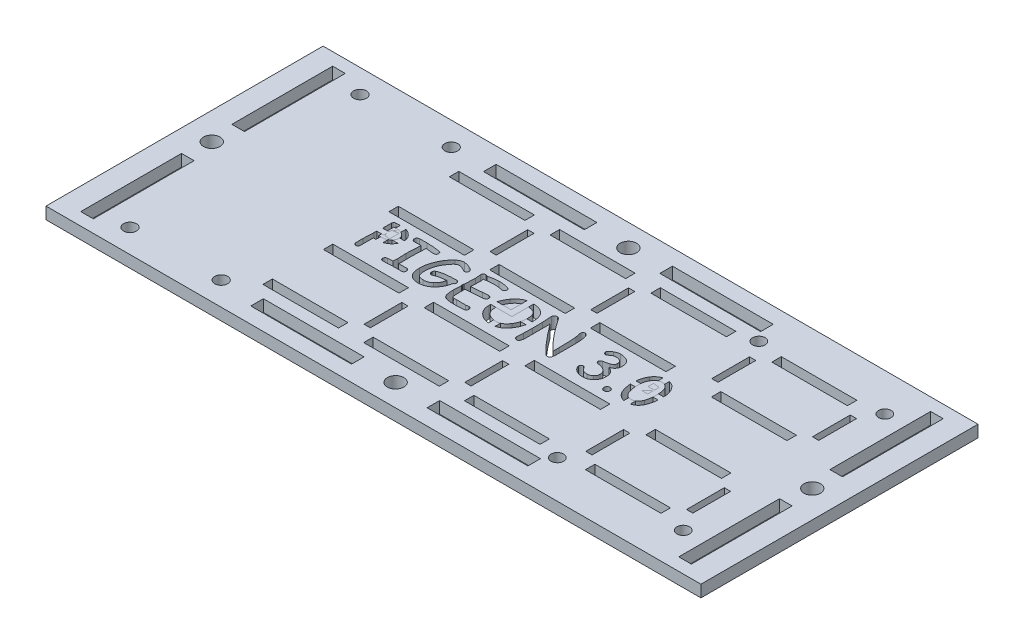
SolidWorks part; units mm, degrees
material "Thornel VCB-20 Carbon Cloth"
ref_plane "Front Plane" through (0, 0, 0) normal (0, 0, 1) x (1, 0, 0)
ref_plane "Top Plane" through (0, 0, 0) normal (0, 1, 0) x (1, 0, 0)
ref_plane "Right Plane" through (0, 0, 0) normal (1, 0, 0) x (0, 0, -1)
sketch "Sketch1" plane through (0, 0, 0) normal (0, 1, 0) x (1, 0, 0)
  line L1 (-82.55, -34.925) -> (82.55, -34.925)
  line L2 (-82.55, -34.925) -> (-82.55, 34.925)
  line L3 (-82.55, 34.925) -> (82.55, 34.925)
  line L4 (82.55, -34.925) -> (82.55, 34.925)
  dimension "D1" = 69.85
  dimension "D2" = 165.1
  dimension "D3" = 34.925
  dimension "D4" = 82.55
extrude "Boss-Extrude1" add sketch "Sketch1" along normal blind 3
sketch "Sketch2" plane through (0, 3, 0) normal (0, 1, 0) x (1, 0, 0)
  line L0 (-82.55, 34.925) -> (-82.55, -34.925) construction
  line L1 (82.55, -34.925) -> (82.55, 34.925) construction
  line L2 (82.55, 34.925) -> (-82.55, 34.925) construction
  line L3 (-82.55, -34.925) -> (82.55, -34.925) construction
  circle A0 centre (-77.47, 29.845) radius 1.5
  circle A1 centre (-77.47, -29.845) radius 1.5
  circle A2 centre (77.47, 29.845) radius 1.5
  circle A3 centre (77.47, -29.845) radius 1.5
  dimension "D1" = 3
  dimension "D2" = 3
  dimension "D3" = 3
  dimension "D4" = 3
  dimension "D5" = 5.08
  dimension "D6" = 5.08
  dimension "D7" = 5.08
  dimension "D8" = 5.08
  dimension "D9" = 5.08
  dimension "D10" = 5.08
  dimension "D11" = 5.08
  dimension "D12" = 5.08
sketch "Sketch3" plane through (0, 3, 0) normal (0, 1, 0) x (1, 0, 0)
  line L0 (-82.55, 34.925) -> (-82.55, -34.925) construction
  line L1 (82.55, -34.925) -> (82.55, 34.925) construction
  line L2 (-82.55, -34.925) -> (82.55, -34.925) construction
  line L3 (82.55, 34.925) -> (-82.55, 34.925) construction
  circle A0 centre (-75.692, 0) radius 2.0828
  circle A1 centre (75.692, 0) radius 2.0828
  circle A2 centre (0, -29.337) radius 2.0828
  circle A3 centre (0, 29.337) radius 2.0828
  dimension "D1" = 6.858
  dimension "D2" = 6.858
  dimension "D3" = 5.588
  dimension "D4" = 5.588
extrude "Cut-Extrude2" cut sketch "Sketch3" against normal blind 5.08
sketch "Sketch4" plane through (0, 3, 0) normal (0, 1, 0) x (1, 0, 0)
  line L0 (-82.55, 34.925) -> (-82.55, -34.925) construction
  line L1 (-44.31, -29) -> (-67.31, -29) construction
  line L2 (-44.31, -29) -> (-44.31, 29) construction
  line L3 (-44.31, 29) -> (-67.31, 29) construction
  line L4 (-67.31, -29) -> (-67.31, 29) construction
  line L5 (-44.31, -29) -> (-67.31, 29) construction
  line L6 (-44.31, 29) -> (-67.31, -29) construction
  circle A0 centre (-67.31, 29) radius 1.625
  circle A1 centre (-44.31, 29) radius 1.625
  circle A2 centre (-44.31, -29) radius 1.625
  circle A3 centre (-67.31, -29) radius 1.625
  point P0 (-55.81, 0)
  dimension "D3" = 3.25
  dimension "D1" = 58
  dimension "D2" = 23
  dimension "D4" = 15.24
extrude "Cut-Extrude3" cut sketch "Sketch4" against normal blind 17.78
sketch "Sketch5" plane through (0, 3, 0) normal (0, 1, 0) x (1, 0, 0)
  line L0 (82.55, 34.925) -> (-82.55, 34.925) construction
  line L1 (68.58, -25.4) -> (36.83, -25.4) construction
  line L2 (68.58, -25.4) -> (68.58, 25.4) construction
  line L3 (68.58, 25.4) -> (36.83, 25.4) construction
  line L4 (36.83, -25.4) -> (36.83, 25.4) construction
  line L5 (68.58, -25.4) -> (36.83, 25.4) construction
  line L6 (68.58, 25.4) -> (36.83, -25.4) construction
  line L7 (-82.55, -34.925) -> (82.55, -34.925) construction
  line L8 (82.55, -34.925) -> (82.55, 34.925) construction
  circle A0 centre (68.58, -25.4) radius 1.5875
  circle A2 centre (68.58, 25.4) radius 1.5875
  circle A3 centre (36.83, 25.4) radius 1.5875
  circle A4 centre (36.83, -25.4) radius 1.5875
  point P0 (52.705, 0)
  dimension "D1" = 9.525
  dimension "D3" = 3.175
  dimension "D2" = 9.525
  dimension "D4" = 31.75
  dimension "D5" = 13.97
extrude "Cut-Extrude4" cut sketch "Sketch5" against normal blind 7.874
sketch "Sketch6" plane through (0, 3, 0) normal (0, 1, 0) x (1, 0, 0)
  line L0 (82.55, 34.925) -> (-82.55, 34.925) construction
  line L1 (-34.925, 27.7495) -> (-9.525, 27.7495)
  line L2 (-34.925, 27.7495) -> (-34.925, 30.9245)
  line L3 (-34.925, 30.9245) -> (-9.525, 30.9245)
  line L4 (-9.525, 27.7495) -> (-9.525, 30.9245)
  line L5 (-34.925, 27.7495) -> (-9.525, 30.9245) construction
  line L6 (-34.925, 30.9245) -> (-9.525, 27.7495) construction
  line L7 (34.925, 30.9245) -> (34.925, 27.7495)
  line L8 (34.925, 30.9245) -> (9.525, 30.9245)
  line L9 (9.525, 30.9245) -> (9.525, 27.7495)
  line L10 (34.925, 27.7495) -> (9.525, 27.7495)
  line L11 (-34.925, -30.9245) -> (-34.925, -27.7495)
  line L12 (-34.925, -27.7495) -> (-9.525, -27.7495)
  line L13 (-9.525, -30.9245) -> (-9.525, -27.7495)
  line L14 (-34.925, -30.9245) -> (-9.525, -30.9245)
  line L15 (34.925, -27.7495) -> (34.925, -30.9245)
  line L16 (34.925, -27.7495) -> (9.525, -27.7495)
  line L17 (9.525, -27.7495) -> (9.525, -30.9245)
  line L18 (34.925, -30.9245) -> (9.525, -30.9245)
  line L19 (-82.55, 34.925) -> (-82.55, -34.925) construction
  line L20 (-76.962, 31.75) -> (-73.787, 31.75)
  line L21 (-76.962, 31.75) -> (-76.962, 6.35)
  line L22 (-76.962, 6.35) -> (-73.787, 6.35)
  line L23 (-73.787, 31.75) -> (-73.787, 6.35)
  line L24 (-76.962, 31.75) -> (-73.787, 6.35) construction
  line L25 (-76.962, 6.35) -> (-73.787, 31.75) construction
  line L26 (-76.962, -6.35) -> (-76.962, -31.75)
  line L27 (-76.962, -6.35) -> (-73.787, -6.35)
  line L28 (-73.787, -6.35) -> (-73.787, -31.75)
  line L29 (-76.962, -31.75) -> (-73.787, -31.75)
  line L30 (-82.55, -34.925) -> (82.55, -34.925) construction
  line L31 (76.962, -31.75) -> (76.962, -6.35)
  line L32 (76.962, -31.75) -> (73.787, -31.75)
  line L33 (73.787, -31.75) -> (73.787, -6.35)
  line L34 (76.962, -6.35) -> (73.787, -6.35)
  line L35 (76.962, 6.35) -> (76.962, 31.75)
  line L36 (76.962, 31.75) -> (73.787, 31.75)
  line L37 (73.787, 6.35) -> (73.787, 31.75)
  line L38 (76.962, 6.35) -> (73.787, 6.35)
  circle A0 centre (0, 29.337) radius 2.0828 construction
  point P0 (-22.225, 29.337)
  point P9 (-75.3745, 19.05)
  point P16 (0, 29.337)
  point P25 (0, 0)
  point P41 (0, 0)
  point P48 (0, 0)
  dimension "D1" = 5.588
  dimension "D2" = 3.175
  dimension "D3" = 25.4
  dimension "D4" = 22.225
  dimension "D7" = 5.588
  dimension "D8" = 3.175
  dimension "D9" = 25.4
  dimension "D10" = 3.175
  dimension "D12" = 3.175
  dimension "D11" = 2
  dimension "D5" = 2
  dimension "D6" = 2
  dimension "D13" = 2
extrude "Cut-Extrude5" cut sketch "Sketch6" against normal blind 10.922
sketch "Sketch7" plane through (0, 3, 0) normal (0, 1, 0) x (1, 0, 0)
  text T0 "PIGEON 3.0" font "Comic Sans MS" height 9.525
  point P1 (-47.03, 0)
  point P6 (-47.03, 0)
extrude "Cut-Extrude6" cut sketch "Sketch7" against normal blind 10.922
sketch "Sketch8" plane through (0, 3, 0) normal (0, 1, 0) x (1, 0, 0)
  line L0 (-37.8032, 1.2942) -> (-33.6782, 1.2942)
  line L1 (-37.8032, 1.2942) -> (-37.8032, 2.6847)
  line L2 (-37.8032, 2.6847) -> (-33.6782, 2.6847)
  line L3 (-27.9753, 1.2942) -> (-27.9753, 2.6847)
  line L4 (-33.6782, -3.5862) -> (-32.1004, -3.5862)
  line L5 (-33.6782, -3.5862) -> (-33.6782, 1.2942)
  line L6 (-33.6782, 7.5651) -> (-32.1004, 7.5651)
  line L7 (-32.1004, -3.5862) -> (-32.1004, 1.2942)
  line L8 (-32.1004, 2.6847) -> (-27.9753, 2.6847)
  line L9 (-33.6782, 2.6847) -> (-33.6782, 7.5651)
  line L10 (-32.1004, 1.2942) -> (-27.9753, 1.2942)
  line L11 (-32.1004, 2.6847) -> (-32.1004, 7.5651)
  line L12 (-5.3977, -0.3316) -> (-1.2727, -0.3316)
  line L13 (-5.3977, -0.3316) -> (-5.3977, 1.059)
  line L14 (-5.3977, 1.059) -> (-1.2727, 1.059)
  line L15 (4.4302, -0.3316) -> (4.4302, 1.059)
  line L16 (-1.2727, -5.212) -> (0.3051, -5.212)
  line L17 (-1.2727, -5.212) -> (-1.2727, -0.3316)
  line L18 (-1.2727, 5.9393) -> (0.3051, 5.9393)
  line L19 (0.3051, -5.212) -> (0.3051, -0.3316)
  line L20 (0.3051, 1.059) -> (4.4302, 1.059)
  line L21 (-1.2727, 1.059) -> (-1.2727, 5.9393)
  line L22 (0.3051, -0.3316) -> (4.4302, -0.3316)
  line L23 (0.3051, 1.059) -> (0.3051, 5.9393)
  line L24 (28.6195, -0.1096) -> (32.7445, -0.1096)
  line L25 (28.6195, -0.1096) -> (28.6195, 1.281)
  line L26 (28.6195, 1.281) -> (32.7445, 1.281)
  line L27 (38.4474, -0.1096) -> (38.4474, 1.281)
  line L28 (32.7445, -4.9899) -> (34.3223, -4.9899)
  line L29 (32.7445, -4.9899) -> (32.7445, -0.1096)
  line L30 (32.7445, 6.1614) -> (34.3223, 6.1614)
  line L31 (34.3223, -4.9899) -> (34.3223, -0.1096)
  line L32 (34.3223, 1.281) -> (38.4474, 1.281)
  line L33 (32.7445, 1.281) -> (32.7445, 6.1614)
  line L34 (34.3223, -0.1096) -> (38.4474, -0.1096)
  line L35 (34.3223, 1.281) -> (34.3223, 6.1614)
extrude "Boss-Extrude2" add sketch "Sketch8" against normal up to surface (3 mm away) up to face at (-25.7661, 0, -0.4919)
sketch "Sketch10" plane through (0, 3, 0) normal (0, 1, 0) x (1, 0, 0)
  line L0 (-38.1, 23.495) -> (-19.05, 23.495) construction
  line L1 (-38.1, 24.6856) -> (-19.05, 24.6856)
  line L2 (-38.1, 24.6856) -> (-38.1, 22.3044)
  line L3 (-38.1, 22.3044) -> (-19.05, 22.3044)
  line L4 (-19.05, 24.6856) -> (-19.05, 22.3044)
  line L5 (-28.575, 24.6856) -> (-28.575, 22.3044)
  line L6 (82.55, 34.925) -> (-82.55, 34.925) construction
  line L7 (-82.55, 34.925) -> (-82.55, -34.925) construction
  line L8 (-12.7, 24.6856) -> (-12.7, 22.3044)
  line L9 (-12.7, 24.6856) -> (6.35, 24.6856)
  line L10 (6.35, 24.6856) -> (6.35, 22.3044)
  line L11 (-12.7, 22.3044) -> (6.35, 22.3044)
  line L12 (12.7, 24.6856) -> (12.7, 22.3044)
  line L13 (12.7, 24.6856) -> (31.75, 24.6856)
  line L14 (31.75, 24.6856) -> (31.75, 22.3044)
  line L15 (12.7, 22.3044) -> (31.75, 22.3044)
  line L16 (-12.7, 9.4456) -> (-12.7, 7.0644)
  line L17 (-12.7, 9.4456) -> (6.35, 9.4456)
  line L18 (6.35, 9.4456) -> (6.35, 7.0644)
  line L19 (-12.7, 7.0644) -> (6.35, 7.0644)
  line L20 (12.7, 9.4456) -> (12.7, 7.0644)
  line L21 (12.7, 9.4456) -> (31.75, 9.4456)
  line L22 (31.75, 9.4456) -> (31.75, 7.0644)
  line L23 (12.7, 7.0644) -> (31.75, 7.0644)
  line L24 (-38.1, 9.4456) -> (-38.1, 7.0644)
  line L25 (-38.1, 9.4456) -> (-19.05, 9.4456)
  line L26 (-19.05, 9.4456) -> (-19.05, 7.0644)
  line L27 (-38.1, 7.0644) -> (-19.05, 7.0644)
  line L28 (-38.1, 24.6856) -> (-12.7, 24.6856) construction
  line L29 (0, 0) -> (-82.55, 0) construction
  line L30 (-38.1, -24.6856) -> (-12.7, -24.6856) construction
  line L31 (-38.1, -23.495) -> (-19.05, -23.495) construction
  line L32 (-38.1, -7.0644) -> (-19.05, -7.0644)
  line L33 (-19.05, -9.4456) -> (-19.05, -7.0644)
  line L34 (-38.1, -9.4456) -> (-19.05, -9.4456)
  line L35 (-38.1, -9.4456) -> (-38.1, -7.0644)
  line L36 (12.7, -7.0644) -> (31.75, -7.0644)
  line L37 (31.75, -9.4456) -> (31.75, -7.0644)
  line L38 (12.7, -9.4456) -> (31.75, -9.4456)
  line L39 (12.7, -9.4456) -> (12.7, -7.0644)
  line L40 (-12.7, -7.0644) -> (6.35, -7.0644)
  line L41 (6.35, -9.4456) -> (6.35, -7.0644)
  line L42 (-12.7, -9.4456) -> (6.35, -9.4456)
  line L43 (-12.7, -9.4456) -> (-12.7, -7.0644)
  line L44 (12.7, -22.3044) -> (31.75, -22.3044)
  line L45 (31.75, -24.6856) -> (31.75, -22.3044)
  line L46 (12.7, -24.6856) -> (31.75, -24.6856)
  line L47 (12.7, -24.6856) -> (12.7, -22.3044)
  line L48 (-12.7, -22.3044) -> (6.35, -22.3044)
  line L49 (6.35, -24.6856) -> (6.35, -22.3044)
  line L50 (-12.7, -24.6856) -> (6.35, -24.6856)
  line L51 (-12.7, -24.6856) -> (-12.7, -22.3044)
  line L52 (-28.575, -24.6856) -> (-28.575, -22.3044)
  line L53 (-19.05, -24.6856) -> (-19.05, -22.3044)
  line L54 (-38.1, -22.3044) -> (-19.05, -22.3044)
  line L55 (-38.1, -24.6856) -> (-38.1, -22.3044)
  line L56 (-38.1, -24.6856) -> (-19.05, -24.6856)
  line L57 (8.7313, 11.1125) -> (8.7313, 20.6375)
  line L58 (-16.6687, 11.1125) -> (-15.0812, 11.1125)
  line L59 (-16.6687, 11.1125) -> (-16.6687, 20.6375)
  line L60 (-16.6687, 20.6375) -> (-15.0812, 20.6375)
  line L61 (-15.0812, 11.1125) -> (-15.0812, 20.6375)
  line L62 (-16.6687, 11.1125) -> (-15.0812, 20.6375) construction
  line L63 (-16.6687, 20.6375) -> (-15.0812, 11.1125) construction
  line L64 (8.7313, 11.1125) -> (10.3188, 11.1125)
  line L65 (10.3188, 11.1125) -> (10.3188, 20.6375)
  line L66 (8.7313, 20.6375) -> (10.3188, 20.6375)
  line L67 (-16.6687, 11.1125) -> (8.7313, 11.1125) construction
  line L68 (-16.6687, -20.6375) -> (-15.0812, -20.6375)
  line L69 (-15.0812, -11.1125) -> (-15.0812, -20.6375)
  line L70 (-16.6687, -11.1125) -> (-15.0812, -11.1125)
  line L71 (-16.6687, -11.1125) -> (-16.6687, -20.6375)
  line L72 (8.7313, -11.1125) -> (10.3188, -11.1125)
  line L73 (10.3188, -11.1125) -> (10.3188, -20.6375)
  line L74 (8.7313, -20.6375) -> (10.3188, -20.6375)
  line L75 (8.7313, -11.1125) -> (8.7313, -20.6375)
  line L76 (43.0033, 24.8834) -> (43.0033, 22.5021)
  line L77 (43.0033, 24.8834) -> (62.0533, 24.8834)
  line L78 (62.0533, 24.8834) -> (62.0533, 22.5021)
  line L79 (43.0033, 22.5021) -> (62.0533, 22.5021)
  line L80 (43.0033, 9.6434) -> (43.0033, 7.2621)
  line L81 (43.0033, 9.6434) -> (62.0533, 9.6434)
  line L82 (62.0533, 9.6434) -> (62.0533, 7.2621)
  line L83 (43.0033, 7.2621) -> (62.0533, 7.2621)
  line L84 (17.6033, 24.8834) -> (43.0033, 24.8834) construction
  line L85 (55.7033, 0.1978) -> (-26.8467, 0.1978) construction
  line L86 (17.6033, -24.4879) -> (43.0033, -24.4879) construction
  line L87 (43.0033, -6.8666) -> (62.0533, -6.8666)
  line L88 (62.0533, -9.2479) -> (62.0533, -6.8666)
  line L89 (43.0033, -9.2479) -> (62.0533, -9.2479)
  line L90 (43.0033, -9.2479) -> (43.0033, -6.8666)
  line L91 (43.0033, -22.1066) -> (62.0533, -22.1066)
  line L92 (62.0533, -24.4879) -> (62.0533, -22.1066)
  line L93 (43.0033, -24.4879) -> (62.0533, -24.4879)
  line L94 (43.0033, -24.4879) -> (43.0033, -22.1066)
  line L95 (64.4346, 11.3103) -> (64.4346, 20.8353)
  line L96 (39.0346, 11.3103) -> (40.6221, 11.3103)
  line L97 (39.0346, 11.3103) -> (39.0346, 20.8353)
  line L98 (39.0346, 20.8353) -> (40.6221, 20.8353)
  line L99 (40.6221, 11.3103) -> (40.6221, 20.8353)
  line L100 (39.0346, 11.3103) -> (40.6221, 20.8353) construction
  line L101 (39.0346, 20.8353) -> (40.6221, 11.3103) construction
  line L102 (64.4346, 11.3103) -> (66.0221, 11.3103)
  line L103 (66.0221, 11.3103) -> (66.0221, 20.8353)
  line L104 (64.4346, 20.8353) -> (66.0221, 20.8353)
  line L105 (39.0346, 11.3103) -> (64.4346, 11.3103) construction
  line L106 (39.0346, -20.4397) -> (40.6221, -20.4397)
  line L107 (40.6221, -10.9147) -> (40.6221, -20.4397)
  line L108 (39.0346, -10.9147) -> (40.6221, -10.9147)
  line L109 (39.0346, -10.9147) -> (39.0346, -20.4397)
  line L110 (64.4346, -10.9147) -> (66.0221, -10.9147)
  line L111 (66.0221, -10.9147) -> (66.0221, -20.4397)
  line L112 (64.4346, -20.4397) -> (66.0221, -20.4397)
  line L113 (64.4346, -10.9147) -> (64.4346, -20.4397)
  point P65 (-15.875, 15.875)
  point P105 (39.8283, 16.0728)
  dimension "D1" = 19.05
  dimension "D2" = 2.3813
  dimension "D3" = 11.43
  dimension "D4" = 44.45
  dimension "D7" = 25.4
  dimension "D8" = 15.24
  dimension "D9" = 1.5875
  dimension "D10" = 3.175
  dimension "D11" = 9.525
  dimension "D12" = 7.62
  dimension "D14" = 25.4
  dimension "D15" = 25.4
  dimension "D16" = 1.5875
  dimension "D17" = 9.525
  dimension "D18" = 25.4
  dimension "D5" = 3
  dimension "D6" = 2
  dimension "D13" = 2
extrude "Cut-Extrude7" cut sketch "Sketch10" against normal blind 16.256 contours L51 L50 L49 L48 | L8 L11 L10 L9 | L32 L33 L34 L35 | L71 L68 L69 L70 | L56 L53 L54 L55 | L40 L41 L42 L43 | L75 L74 L73 L72 | L38 L37 L36 L39 | L44 L45 L46 L47 | L21 L22 L23 L20 | L57 L66 L65 L64 | L13 L14 L15 L12 | L17 L18 L19 L16 | L59 L60 L61 L58 | L27 L26 L25 L24 | L3 L4 L1 L2 | L80 L83 L82 L81 | L76 L79 L78 L77 | L95 L104 L103 L102 | L96 L99 L98 L97 | L91 L92 L93 L94 | L110 L111 L112 L113 | L87 L88 L89 L90 | L106 L107 L108 L109 region at (-3.175, 3, -23.495) region at (-3.175, 3, 23.495)
